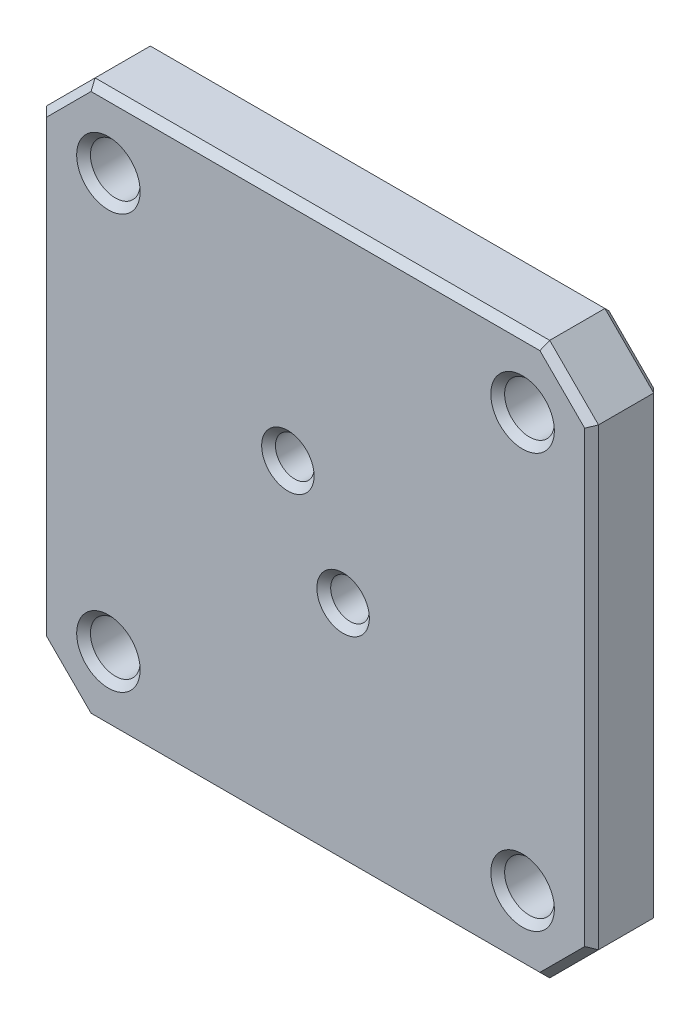
SolidWorks part; units mm, degrees
ref_plane "Top" through (0, 0, 0) normal (0, 0, 1) x (1, 0, 0)
ref_plane "Front" through (0, 0, 0) normal (0, 1, 0) x (1, 0, 0)
ref_plane "Right" through (0, 0, 0) normal (1, 0, 0) x (0, 0, -1)
sketch "Sketch1" plane through (0, 0, 0) normal (0, 0, 1) x (1, 0, 0)
  line L1 (0, 0) -> (40, 0)
  line L2 (0, 0) -> (0, 40)
  line L3 (0, 40) -> (40, 40)
  line L4 (40, 0) -> (40, 40)
  dimension "D1" = 40
  dimension "D2" = 40
extrude "Boss-Extrude1" add sketch "Sketch1" along normal blind 5
sketch "Sketch2" plane through (0, 0, 5) normal (0, 0, 1) x (1, 0, 0)
  line L0 (40, 40) -> (0, 40) construction
  line L1 (5, 35) -> (35, 35) construction
  line L2 (5, 35) -> (5, 5) construction
  line L3 (5, 5) -> (35, 5) construction
  line L4 (35, 35) -> (35, 5) construction
  line L5 (0, 40) -> (0, 0) construction
  circle A0 centre (5, 35) radius 1.8
  circle A1 centre (35, 35) radius 1.8
  circle A2 centre (5, 5) radius 1.8
  circle A3 centre (35, 5) radius 1.8
  dimension "D5" = 3.6
  dimension "D1" = 30
  dimension "D2" = 30
  dimension "D3" = 5
  dimension "D4" = 5
extrude "Cut-Extrude1" cut sketch "Sketch2" against normal blind 5
sketch "Sketch3" plane through (0, 0, 5) normal (0, 0, 1) x (1, 0, 0)
  line L0 (18, 23.4641) -> (22, 16.5359) construction
  line L1 (40, 0) -> (40, 40) construction
  line L2 (0, 40) -> (0, 0) construction
  line L3 (40, 40) -> (0, 40) construction
  circle A0 centre (18, 23.4641) radius 1.4
  circle A1 centre (22, 16.5359) radius 1.4
  point P4 (20, 20)
  dimension "D5" = 2.8
  dimension "D1" = 30
  dimension "D2" = 8
  dimension "D3" = 20
  dimension "D4" = 20
extrude "Cut-Extrude2" cut sketch "Sketch3" against normal blind 5
chamfer "Chamfer1" distance 3.536 angle 45 4 edges at (0, 40, 2.5) (40, 40, 2.5) (40, 0, 2.5) (0, 0, 2.5)
chamfer "Chamfer2" distance 0.5 angle 45 28 edges at (1.768, 1.768, 0) (20, 0, 0) (38.232, 1.768, 0) (40, 20, 0) (38.232, 38.232, 0) (20, 40, 0) (1.768, 38.232, 0) (0, 20, 0) (6.8, 35, 0) (36.8, 5, 0) (6.8, 5, 0) (36.8, 35, 0) (23.4, 16.5359, 0) (19.4, 23.4641, 0) (38.232, 38.232, 5) (40, 20, 5) (38.232, 1.768, 5) (20, 0, 5) (1.768, 1.768, 5) (0, 20, 5) (1.768, 38.232, 5) (20, 40, 5) (6.8, 35, 5) (36.8, 5, 5) (6.8, 5, 5) (36.8, 35, 5) (23.4, 16.5359, 5) (19.4, 23.4641, 5)
